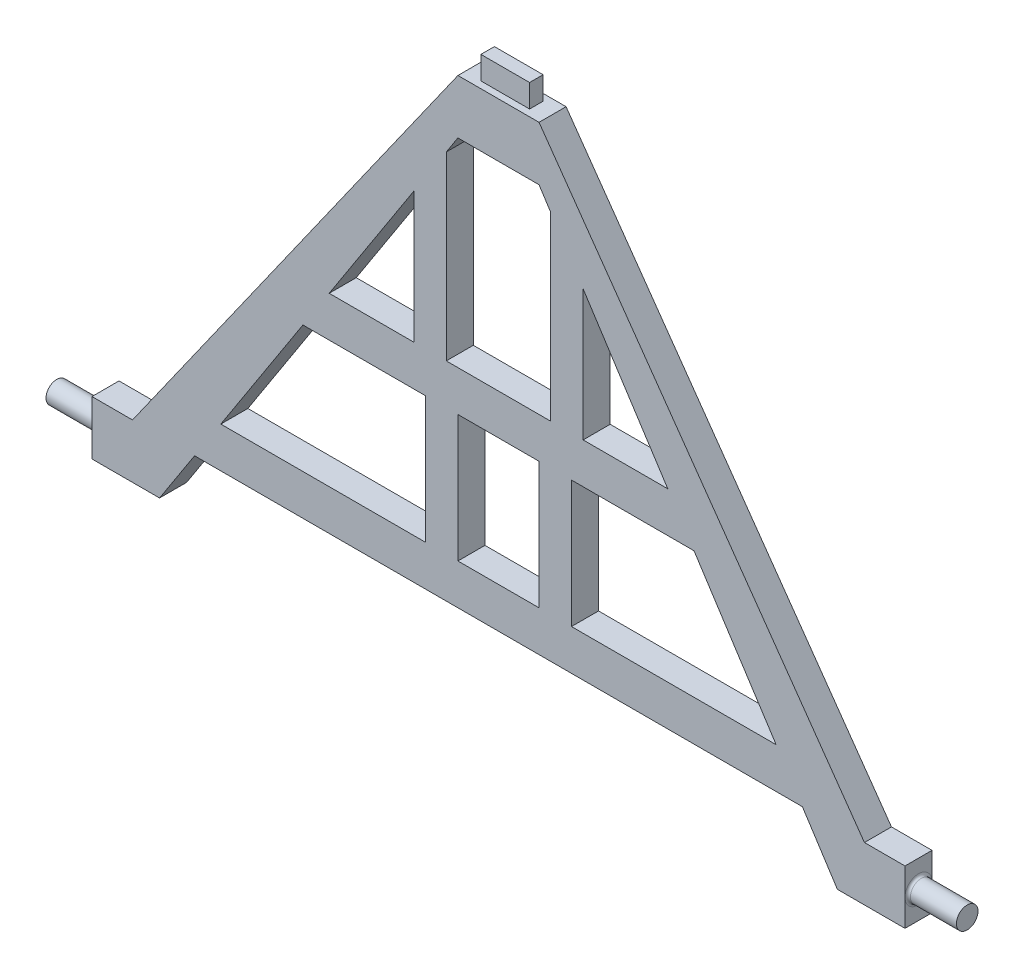
SolidWorks part; units mm, degrees
ref_plane "Front Plane" through (0, 0, 0) normal (0, 0, 1) x (1, 0, 0)
ref_plane "Top Plane" through (0, 0, 0) normal (0, 1, 0) x (1, 0, 0)
ref_plane "Right Plane" through (0, 0, 0) normal (1, 0, 0) x (0, 0, -1)
sketch "Sketch2" plane through (0, 0, 0) normal (0, 0, 1) x (1, 0, 0)
  line L0 (0, 38.6427) -> (15, 38.6427)
  line L2 (135.3384, -111.8573) -> (150.3384, -111.8573)
  line L3 (150.3384, -111.8573) -> (150.3384, -131.8573)
  line L4 (150.3384, -131.8573) -> (125.3384, -131.8573)
  line L6 (15, 58.6427) -> (0, 58.6427)
  line L7 (0, 58.6427) -> (0, 38.6427)
  line L8 (15, 38.6427) -> (125.3384, -131.8573)
  line L9 (135.3384, -111.8573) -> (15, 58.6427)
  line L10 (62.6119, -34.9295) -> (0, -34.9295)
  line L11 (0, -34.9295) -> (0, -49.9295)
  line L12 (0, -49.9295) -> (72.3191, -49.9295)
  line L13 (112.3955, -111.8573) -> (0, -111.8573)
  line L14 (0, -111.8573) -> (0, -96.8573)
  line L15 (0, -96.8573) -> (102.6883, -96.8573)
  line L16 (15, -96.8573) -> (15, -49.9295)
  line L17 (15, -49.9295) -> (27, -49.9295)
  line L18 (27, -49.9295) -> (27, -96.8573)
  line L19 (27, -96.8573) -> (15, -96.8573)
  line L20 (31.306, -34.9295) -> (31.306, 13.4459)
  line L21 (31.306, 13.4459) -> (19.306, 13.4459)
  line L22 (19.306, 13.4459) -> (19.306, -34.9295)
  line L23 (19.306, -34.9295) -> (31.306, -34.9295)
  line L24 (19.306, 13.4459) -> (19.306, 38.6427)
  dimension "D1" = 190.5
  dimension "D2" = 20
  dimension "D3" = 20
  dimension "D4" = 25
  dimension "D5" = 15
  dimension "D6" = 15
  dimension "D7" = 15
  dimension "D8" = 15
  dimension "D9" = 12
  dimension "D10" = 15
  dimension "D11" = 12
extrude "Boss-Extrude1" add sketch "Sketch2" along normal blind 10 contours L2 L9 L6 L7 L0 L8 L4 L3 | L24 L21 L8 L0 | L21 L22 L10 L20 | L11 L12 L8 L10 | L18 L12 L16 L15 | L15 L14 L13 L8 region at (78.8633, -45.0935, 0) region at (23.306, 19.6269, 0) region at (25.306, -10.7418, 0) region at (33.791, -42.6093, 0) region at (53.8075, -104.4702, 0) region at (21, -73.3934, 0)
sketch "Sketch6" plane through (150.3384, 0, 0) normal (1, 0, 0) x (0, 0, -1)
  line L0 (0, -111.8573) -> (0, -131.8573) construction
  line L3 (-10, -111.8573) -> (0, -111.8573) construction
  circle A0 centre (-5, -121.8573) radius 4
  dimension "D1" = 8
  dimension "D2" = 5
  dimension "D3" = 10
extrude "Boss-Extrude3" add sketch "Sketch6" along normal blind 18
fillet "Fillet2" radius 1 1 edges at (150.3384, -117.8573, 5)
mirror "Mirror1" about plane through (0, 0, 10) normal (1, 0, 0) of "Fillet2", "Boss-Extrude1", "Boss-Extrude3"
sketch "Sketch7" plane through (0, 58.6427, 0) normal (0, 1, 0) x (1, 0, 0)
  line L0 (15, 0) -> (-15, 0) construction
  line L1 (9, -7.5) -> (-9, -7.5)
  line L2 (9, -7.5) -> (9, -2.5)
  line L3 (9, -2.5) -> (-9, -2.5)
  line L4 (-9, -7.5) -> (-9, -2.5)
  line L11 (15, -10) -> (15, 0) construction
  dimension "D1" = 2.5
  dimension "D2" = 5
  dimension "D3" = 18
  dimension "D4" = 6
extrude "Boss-Extrude4" add sketch "Sketch7" along normal blind 8.5
